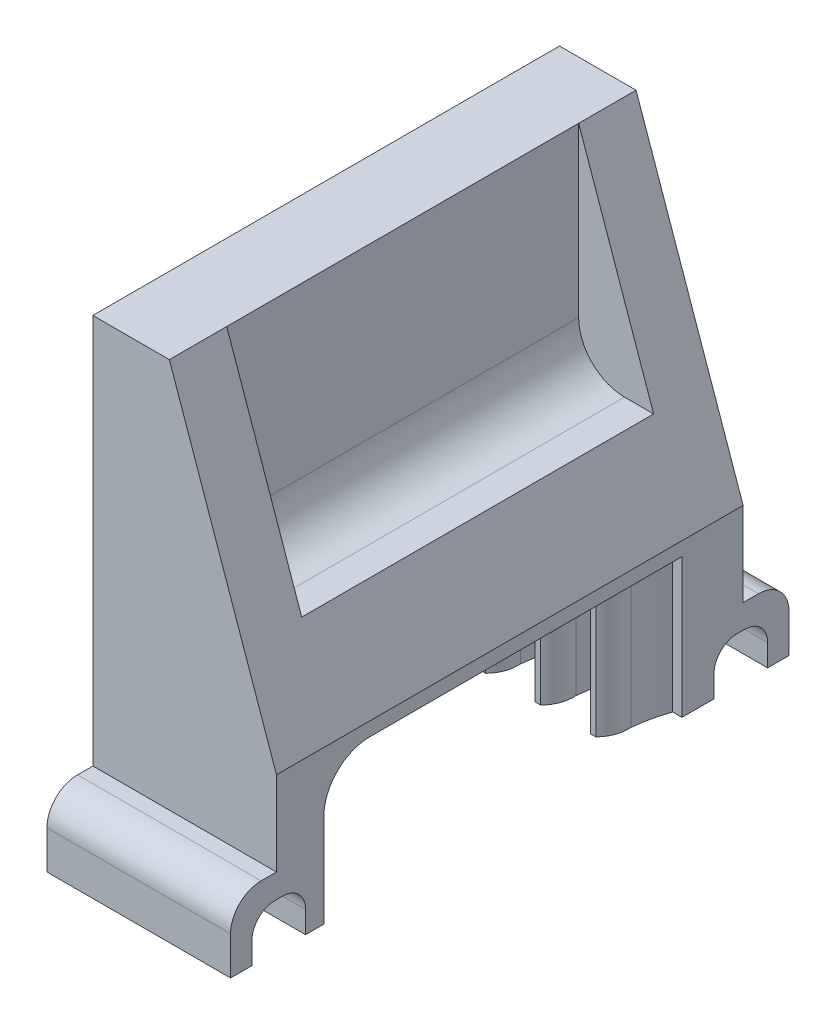
SolidWorks part; units mm, degrees
ref_plane "Front Plane" through (0, 0, 0) normal (0, 0, 1) x (1, 0, 0)
ref_plane "Top Plane" through (0, 0, 0) normal (0, 1, 0) x (1, 0, 0)
ref_plane "Right Plane" through (0, 0, 0) normal (1, 0, 0) x (0, 0, -1)
sketch "Sketch1" plane through (0, 0, 0) normal (0, 0, 1) x (1, 0, 0)
  line L0 (0, 0) -> (0, -30)
  line L1 (0, -30) -> (12, -30)
  line L2 (12, -30) -> (12, -20)
  line L3 (12, -20) -> (5, 0)
  line L4 (5, 0) -> (0, 0)
  dimension "D1" = 30
  dimension "D2" = 12
  dimension "D3" = 10
  dimension "D4" = 5
extrude "Boss-Extrude1" add sketch "Sketch1" against normal blind 30.5
sketch "Sketch4" plane through (0, 0, 0) normal (-1, 0, 0) x (0, 0, 1)
  line L0 (-30.5, 0) -> (-30.5, -30) construction
  line L1 (-26.5, -20.8999) -> (-3.1, -20.8999)
  line L2 (-26.5, -20.8999) -> (-26.5, -30.8999)
  line L3 (-26.5, -30.8999) -> (-3.1, -30.8999)
  line L4 (-3.1, -20.8999) -> (-3.1, -30.8999)
  point P4 (-26.5, -25.8999)
  dimension "D1" = 23.4
  dimension "D2" = 10
  dimension "D3" = 4
extrude "Cut-Extrude2" cut sketch "Sketch4" against normal blind 25 contours L2 L1 L4 L3
ref_plane "Plane1" through (0, 0, -15.25) normal (0, 0, 1) x (1, 0, 0)
sketch "Sketch6" plane through (0, 0, -15.25) normal (0, 0, 1) x (1, 0, 0)
  line L0 (5, 0) -> (5, -14)
  line L1 (5, -14) -> (9.9, -14)
  line L2 (12, -20) -> (5, 0) construction
  line L3 (9.9, -14) -> (5, 0)
  dimension "D1" = 14
extrude "Cut-Extrude4" cut sketch "Sketch6" against normal mid plane 23
ref_plane "Plane2" through (0, -26.4, 0) normal (0, 1, 0) x (1, 0, 0)
ref_plane "Plane3" through (0, -30, 0) normal (0, 1, 0) x (1, 0, 0)
sketch "Sketch7" plane through (0, -30, 0) normal (0, 1, 0) x (1, 0, 0)
  line L0 (11.2768, 28.25) -> (-19.7232, 28.25)
  line L62 (-6.6, 15.25) -> (6.6, 15.25) construction
  line L162 (11.2768, 28.25) -> (11.2768, 26.55)
  line L172 (-19.7232, 26.55) -> (-19.7232, 28.25)
  line L243 (11.2768, 26.55) -> (-19.7232, 26.55)
  dimension "D2" = 31
  dimension "D3" = 1.7
  dimension "D7" = 13
extrude "Boss-Extrude3" add sketch "Sketch7" along normal up to surface (9.1001 mm away) up to face at (6, -20.8999, -14.8)
sketch "Sketch10" plane through (0, -20.8999, 0) normal (0, 1, 0) x (1, 0, 0)
  line L1 (10.1114, 22.5807) -> (10.1114, 23.4692) construction
  line L2 (10.2915, 22.5807) -> (9.9312, 22.5807)
  line L4 (-19.7232, 26.55) -> (0, 26.55) construction
  line L5 (8.8114, 26.55) -> (11.4114, 26.55)
  arc A0 (10.2915, 22.5807) -> (10.902, 24.2589) centre (8.7521, 24.0909) ccw
  arc A1 (10.902, 24.2589) -> (11.4114, 26.55) centre (20.4547, 23.3375) cw
  arc A2 (9.3207, 24.2589) -> (8.8114, 26.55) centre (-0.232, 23.3375) ccw
  arc A3 (9.9312, 22.5807) -> (9.3207, 24.2589) centre (11.4706, 24.0909) cw
  dimension "D1" = 2.6
extrude "Boss-Extrude4" add sketch "Sketch10" against normal up to surface (9.1001 mm away) up to face at (-1.9308, -30, -27.95)
pattern_linear "LPattern1" count 8 spacing 3.6 along (-1, 0, 0) of "Boss-Extrude4"
sketch "Sketch11" plane through (0, 0, -30.5) normal (0, 0, -1) x (-1, 0, 0)
  line L0 (-12, -30) -> (-12, -20) construction
  line L1 (-12, -25.5) -> (0, -25.5)
  line L2 (-12, -25.5) -> (-12, -30)
  line L3 (-12, -30) -> (0, -30)
  line L4 (0, -25.5) -> (0, -30)
  dimension "D1" = 4.5
extrude "Boss-Extrude5" add sketch "Sketch11" along normal blind 3
fillet "Fillet1" radius 2 1 edges at (6, -25.5, -33.5)
mirror "Mirror1" about plane through (0, 0, -15.25) normal (0, 0, 1) of "Boss-Extrude5"
fillet "Fillet2" radius 2 1 edges at (6, -25.5, 3)
fillet "Fillet5" radius 3 2 edges at (5, -14, -15.25) (6, -20.8999, -3.1)
sketch "Sketch12" plane through (0, 0, 0) normal (-1, 0, 0) x (0, 0, 1)
  line L0 (-15.25, -20.6354) -> (-15.25, -36.9741) construction
  line L1 (-32.1, -27.0644) -> (-28.6, -27.0644)
  line L2 (-32.1, -27.0644) -> (-32.1, -30.5644)
  line L3 (-32.1, -30.5644) -> (-28.6, -30.5644)
  line L4 (-28.6, -27.0644) -> (-28.6, -30.5644)
  line L5 (-3.1, -30) -> (-3.1, -23.8999) construction
  line L11 (-15.25, -16.5) -> (-15.25, 16.5) construction
  line L12 (1.6, -30.5644) -> (-1.9, -30.5644)
  line L13 (-1.9, -27.0644) -> (-1.9, -30.5644)
  line L14 (1.6, -27.0644) -> (-1.9, -27.0644)
  line L15 (1.6, -27.0644) -> (1.6, -30.5644)
  dimension "D1" = 3.5
  dimension "D2" = 3.5
  dimension "D3" = 1.2
extrude "Cut-Extrude5" cut sketch "Sketch12" against normal up to surface (12 mm away) up to face at (12, -25.4167, -14.4786)
fillet "Fillet6" radius 1.5 4 edges at (6, -27.0644, -32.1) (6, -27.0644, -28.6) (6, -27.0644, 1.6) (6, -27.0644, -1.9)
